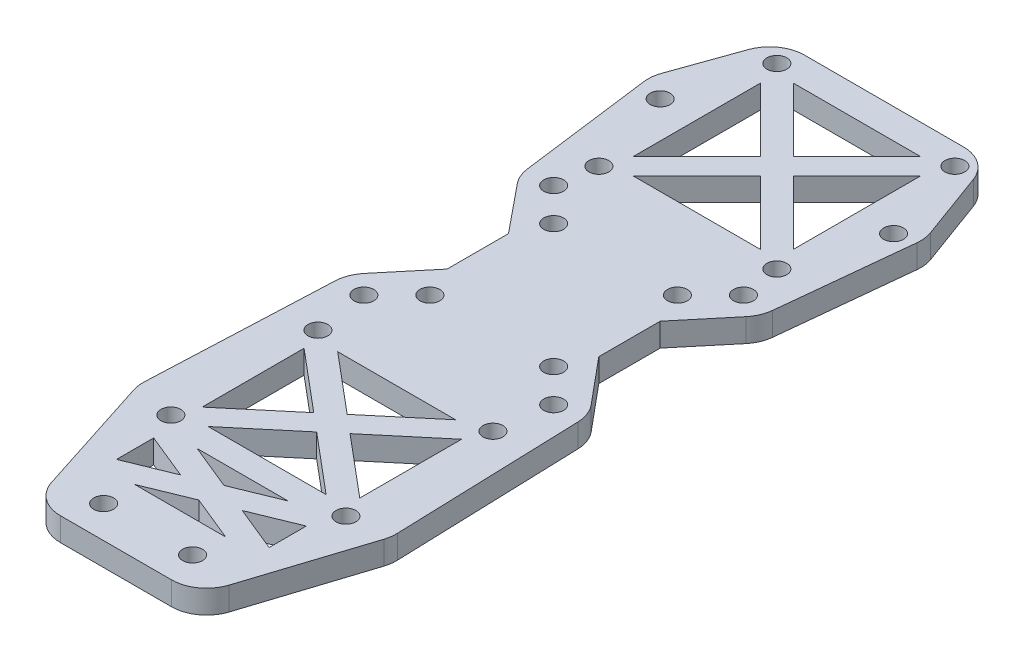
SolidWorks part; units mm, degrees
ref_plane "Front Plane" through (0, 0, 0) normal (0, 0, 1) x (1, 0, 0)
ref_plane "Top Plane" through (0, 0, 0) normal (0, 1, 0) x (1, 0, 0)
ref_plane "Right Plane" through (0, 0, 0) normal (1, 0, 0) x (0, 0, -1)
sketch "Sketch1" plane through (0, 0, 0) normal (0, 1, 0) x (1, 0, 0)
  line L22 (0, 8) -> (0, 23) construction
  line L23 (-10.5, -8) -> (10.5, -8) construction
  line L24 (-10.5, -8) -> (-10.5, 8) construction
  line L25 (-10.5, 8) -> (10.5, 8) construction
  line L26 (10.5, -8) -> (10.5, 8) construction
  line L27 (-20, 20) -> (-69.4975, 69.4975) construction
  line L28 (-20, -20) -> (-69.4975, -69.4975) construction
  line L29 (0, -8) -> (0, -38) construction
  line L31 (-15.25, 23) -> (15.25, 23) construction
  line L32 (-15.25, 23) -> (-15.25, 53.5) construction
  line L33 (-15.25, 53.5) -> (15.25, 53.5) construction
  line L34 (15.25, 23) -> (15.25, 53.5) construction
  line L35 (-15.25, 23) -> (15.25, 53.5) construction
  line L36 (-15.25, 53.5) -> (15.25, 23) construction
  line L41 (-2.2741, -34.7838) -> (-12.1911, -26.4535)
  line L42 (-1.5547, -38) -> (-13.4775, -48.0151)
  line L45 (20, -20) -> (69.4975, -69.4975) construction
  line L46 (-9.5155, -74.9948) -> (9.5155, -74.9948)
  line L53 (0, 95) -> (0, -95) construction
  line L59 (-20, -75) -> (20, 75) construction
  line L60 (-20, 75) -> (20, -75) construction
  line L61 (20, 20) -> (-20, -20) construction
  line L62 (-1.5547, -38) -> (1.5547, -38)
  line L63 (0, -35.152) -> (0, -40.848)
  line L64 (20, -20) -> (-20, 20) construction
  line L66 (0, -35.152) -> (-5.3238, -20.9553)
  line L69 (20, 20) -> (69.4975, 69.4975) construction
  line L70 (-14.1084, 57.113) -> (13.1312, 57.113)
  line L71 (2.2741, -34.7838) -> (7.1964, -21.6575)
  line L72 (0, -35.152) -> (5.3238, -20.9553)
  line L73 (1.5547, -38) -> (13.4775, -48.0151)
  line L74 (1.5547, -38) -> (13.4775, -27.9849)
  line L75 (-2.2741, -34.7838) -> (-7.1964, -21.6575)
  line L76 (2.2741, -34.7838) -> (12.1911, -26.4535)
  line L77 (2.2741, -41.2162) -> (7.1964, -54.3425)
  line L78 (-1.5547, -38) -> (-13.4775, -27.9849)
  line L79 (-2.2741, -41.2162) -> (-7.1964, -54.3425)
  line L80 (-2.2741, -41.2162) -> (-12.1911, -49.5465)
  line L81 (0, -40.848) -> (5.3238, -55.0447)
  line L82 (0, -40.848) -> (-5.3238, -55.0447)
  line L83 (2.2741, -41.2162) -> (12.1911, -49.5465)
  line L84 (20, 0) -> (-20, 0) construction
  line L86 (-13, -5.2632) -> (-13, 5.2632)
  line L87 (13, -5.2632) -> (13, 5.2632)
  line L92 (-13, -8) -> (-13, 8) construction
  line L93 (13, -8) -> (13, 8) construction
  line L95 (-26.1774, -26.1774) -> (26.1774, -26.1774) construction
  line L96 (-26.1774, -26.1774) -> (-26.1774, 26.1774) construction
  line L97 (-26.1774, 26.1774) -> (26.1774, 26.1774) construction
  line L98 (26.1774, -26.1774) -> (26.1774, 26.1774) construction
  line L99 (-26.1774, -26.1774) -> (26.1774, 26.1774) construction
  line L100 (-26.1774, 26.1774) -> (26.1774, -26.1774) construction
  line L101 (-19.7604, 53.1268) -> (-23.659, 42.1845)
  line L102 (-13, 5.2632) -> (-19.6727, 13.4492)
  line L103 (-15.2273, -70.8321) -> (-21.92, -50.0261)
  line L104 (-13, -5.2632) -> (-19.4568, -13.0215)
  line L105 (15.2273, -70.8321) -> (21.6746, -50.7889)
  line L106 (13, -5.2632) -> (19.5205, -13.0981)
  line L107 (13, 5.2632) -> (19.6704, 13.2781)
  line L108 (18.7641, 53.1794) -> (23.0196, 41.5787)
  line L109 (-23.9568, 39.3962) -> (-20.9718, 16.4656)
  line L110 (21.0264, 16.4959) -> (23.3545, 38.892)
  line L111 (21.9596, -48.7542) -> (20.9055, -16.7388)
  line L112 (-22.2025, -47.928) -> (-20.8394, -16.5988)
  circle A4 centre (15.25, 53.5) radius 1.4712 construction
  circle A5 centre (15.25, 23) radius 1.6691 construction
  circle A6 centre (-15.25, 23) radius 1.8297 construction
  circle A7 centre (-15.25, 53.5) radius 1.9203 construction
  arc A12 (-12.1911, -26.4535) -> (-13.4775, -27.9849) centre (-15, -25.4) ccw
  arc A13 (12.1911, -26.4535) -> (13.4775, -27.9849) centre (15, -25.4) cw
  arc A14 (12.1911, -49.5465) -> (13.4775, -48.0151) centre (15, -50.6) ccw
  arc A15 (-12.1911, -49.5465) -> (-13.4775, -48.0151) centre (-15, -50.6) cw
  arc A16 (7.1964, -21.6575) -> (5.3238, -20.9553) centre (7.62, -17.68) ccw
  arc A17 (-5.3238, -20.9553) -> (-7.1964, -21.6575) centre (-7.62, -17.68) ccw
  arc A18 (-7.1964, -54.3425) -> (-5.3238, -55.0447) centre (-7.62, -58.32) ccw
  arc A19 (5.3238, -55.0447) -> (7.1964, -54.3425) centre (7.62, -58.32) ccw
  arc A30 (-14.1084, 57.113) -> (-19.7604, 53.1268) centre (-14.1084, 51.113) ccw
  arc A31 (13.1312, 57.113) -> (18.7641, 53.1794) centre (13.1312, 51.113) cw
  circle A32 centre (-7.62, -69.4975) radius 1.7273
  circle A33 centre (7.62, -69.4975) radius 1.8852
  arc A34 (15.2273, -70.8321) -> (9.5155, -74.9948) centre (9.5155, -68.9948) cw
  arc A35 (-15.2273, -70.8321) -> (-9.5155, -74.9948) centre (-9.5155, -68.9948) ccw
  circle A38 centre (-20, 38.25) radius 1.5
  circle A39 centre (20, 38.25) radius 1.5
  arc A40 (21.9596, -48.7542) -> (21.6746, -50.7889) centre (15.9628, -48.9516) cw
  arc A41 (-22.2025, -47.928) -> (-21.92, -50.0261) centre (-16.2082, -48.1888) ccw
  arc A42 (-20.8394, -16.5988) -> (-19.4568, -13.0215) centre (-14.845, -16.8597) cw
  arc A43 (20.9055, -16.7388) -> (19.5205, -13.0981) centre (14.9087, -16.9362) ccw
  arc A44 (23.3545, 38.892) -> (23.0196, 41.5787) centre (17.3867, 39.5123) ccw
  arc A45 (21.0264, 16.4959) -> (19.6704, 13.2781) centre (15.0586, 17.1163) cw
  arc A46 (-20.9718, 16.4656) -> (-19.6727, 13.4492) centre (-15.022, 17.2401) ccw
  arc A47 (-23.9568, 39.3962) -> (-23.659, 42.1845) centre (-18.007, 40.1708) cw
  point P0 (0, 0)
  point P1 (0, 0)
  point P2 (0, 0)
  point P6 (0, -38)
  point P9 (0, 0)
  point P17 (0, 38.25)
  point P83 (0, 0)
  dimension "D42" = 3
  dimension "D43" = 3
  dimension "D44" = 4
  dimension "D45" = 4
  dimension "D46" = 3
  dimension "D47" = 3
  dimension "D48" = 4
  dimension "D49" = 4
  dimension "D51" = 6
  dimension "D52" = 6
  dimension "D55" = 6
  dimension "D59" = 6
  dimension "D60" = 3
  dimension "D1" = 21
  dimension "D3" = 40
  dimension "D4" = 16
  dimension "D5" = 15
  dimension "D6" = 30
  dimension "D7" = 30.5
  dimension "D8" = 30.5
  dimension "D9" = 0
  dimension "D10" = 70
  dimension "D11" = 70
  dimension "D12" = 45
  dimension "D13" = 45
  dimension "D14" = 70
  dimension "D15" = 70
  dimension "D16" = 19.5898
  dimension "D17" = 21.7018
  dimension "D18" = 20.32
  dimension "D19" = 12.6
  dimension "D20" = 19.5898
  dimension "D21" = 0
  dimension "D22" = 150
  dimension "D23" = 21.7018
  dimension "D24" = 21.7018
  dimension "D25" = 19.5898
  dimension "D26" = 15.5709
  dimension "D27" = 12.9514
  dimension "D28" = 13.1263
  dimension "D29" = 15.1621
  dimension "D30" = 15.1621
  dimension "D31" = 14.0189
  dimension "D32" = 12.9514
  dimension "D33" = 15.5709
  dimension "D34" = 15.5709
  dimension "D35" = 12.9514
  dimension "D36" = 14.0189
  dimension "D37" = 15.1621
  dimension "D38" = 15.1621
  dimension "D39" = 14.0189
  dimension "D40" = 12.9514
  dimension "D41" = 15.5709
  dimension "D50" = 0
  dimension "D61" = 20
  dimension "D62" = 18.25
  dimension "D63" = 18.25
  dimension "D64" = 20
  dimension "D53" = 2.5
  dimension "D54" = 2.5
extrude "Boss-Extrude1" add sketch "Sketch1" along normal blind 4 contours L70 A31 L108 A44 L110 A45 L107 L87 L106 A43 L111 A40 L105 A34 L46 A35 L103 A41 L112 A42 L104 L86 L102 A46 L109 A47 L101 A30
sketch "Sketch7" plane through (0, 4, 0) normal (0, 1, 0) x (1, 0, 0)
  point P0 (7.62, -69.4975)
  point P2 (-7.62, -69.4975)
  point P4 (-26.1774, -26.1774)
  point P6 (26.1774, -26.1774)
  point P8 (26.1774, 26.1774)
  point P10 (-26.1774, 26.1774)
  point P13 (-15, -25.4)
  point P15 (-15.25, 23)
  point P17 (-15.25, 53.5)
  point P19 (15.25, 53.5)
  point P21 (15.25, 23)
  point P23 (-15, -50.6)
  point P25 (15, -50.6)
  point P27 (15, -25.4)
  point P30 (20, 38.25)
  point P32 (-20, 38.25)
sketch "Sketch6" plane through (0, 4, 0) normal (0, 1, 0) x (1, 0, 0)
  line L0 (-9.5155, -74.9948) -> (9.5155, -74.9948) construction
  line L1 (-15.25, 23) -> (15.25, 23) construction
  line L2 (-15.25, 23) -> (-15.25, 53.5) construction
  line L3 (-15.25, 53.5) -> (15.25, 53.5) construction
  line L4 (15.25, 23) -> (15.25, 53.5) construction
  line L5 (-15, -50.6) -> (15, -50.6) construction
  line L6 (-15, -50.6) -> (-15, -25.4) construction
  line L7 (-15, -25.4) -> (15, -25.4) construction
  line L8 (15, -50.6) -> (15, -25.4) construction
  line L9 (-9.5155, -74.9948) -> (9.5155, -74.9948)
  line L12 (-15, -50.6) -> (15, -25.4) construction
  line L13 (-15, -25.4) -> (15, -50.6) construction
  line L14 (-13.75, 24.5) -> (13.75, 52) construction
  line L15 (-10.9216, 24.5) -> (10.9216, 24.5)
  line L16 (0, 200095) -> (0, -200095) construction
  line L17 (-7.7916, -53.3037) -> (7.7916, -53.3037)
  line L18 (-13.0763, -55.4644) -> (-13.0763, -61.8357)
  line L19 (13.75, 27.3284) -> (2.8284, 38.25)
  line L20 (-10.9216, 24.5) -> (0, 35.4216)
  line L21 (-13.5, -29.272) -> (-3.1095, -38)
  line L22 (-10.1048, -49.1) -> (0, -40.612)
  line L24 (-7.7916, -63.9964) -> (7.7916, -63.9964)
  line L26 (10.9216, 24.5) -> (0, 35.4216)
  line L27 (-13.75, 27.3284) -> (-2.8284, 38.25)
  line L28 (-13.5, -46.728) -> (-13.5, -29.272)
  line L29 (-13.5, -46.728) -> (-3.1095, -38)
  line L32 (13.0763, -55.4644) -> (13.0763, -61.8357)
  line L33 (-13.75, 27.3284) -> (-13.75, 49.1716)
  line L34 (0, 41.0784) -> (10.9216, 52)
  line L35 (-2.8284, 38.25) -> (-13.75, 49.1716)
  line L36 (2.8284, 38.25) -> (13.75, 49.1716)
  line L37 (0, 41.0784) -> (-10.9216, 52)
  line L38 (-10.1048, -26.9) -> (10.1048, -26.9)
  line L39 (-13.75, 23) -> (-13.75, 53.5) construction
  line L40 (-10.9216, 52) -> (10.9216, 52)
  line L41 (-15.25, 23) -> (15.25, 53.5) construction
  line L42 (0, -35.388) -> (10.1048, -26.9)
  line L43 (-16.6642, 24.4142) -> (13.8358, 54.9142) construction
  line L44 (-10.1048, -49.1) -> (10.1048, -49.1)
  line L45 (-13.8358, 21.5858) -> (16.6642, 52.0858) construction
  line L46 (13.75, 24.5) -> (-13.75, 52) construction
  line L47 (13.75, 27.3284) -> (13.75, 49.1716)
  line L48 (0, -40.612) -> (10.1048, -49.1)
  line L49 (-16.2864, -26.9314) -> (13.7136, -52.1314) construction
  line L50 (-15, -26.9) -> (15, -26.9) construction
  line L51 (3.1095, -38) -> (13.5, -29.272)
  line L52 (-10.1048, -26.9) -> (0, -35.388)
  line L53 (-16.2864, -49.0686) -> (13.7136, -23.8686) construction
  line L54 (-13.7136, -52.1314) -> (16.2864, -26.9314) construction
  line L55 (-15, -49.1) -> (15, -49.1) construction
  line L56 (13.5, -46.728) -> (13.5, -29.272)
  line L57 (3.1095, -38) -> (13.5, -46.728)
  line L58 (-13.0763, -53.3037) -> (13.0763, -63.9964) construction
  line L59 (-13.0763, -63.9964) -> (13.0763, -53.3037) construction
  line L60 (-7.7916, -63.9964) -> (0, -60.8108)
  line L61 (-13.0763, -55.4644) -> (-5.2847, -58.6501)
  line L62 (-13.0763, -61.8357) -> (-5.2847, -58.6501)
  line L63 (-7.7916, -53.3037) -> (0, -56.4893)
  line L64 (-12.3194, -51.4524) -> (13.8332, -62.1452) construction
  line L65 (-13.8332, -55.1549) -> (12.3194, -65.8477) construction
  line L66 (-13.8332, -62.1452) -> (12.3194, -51.4524) construction
  line L67 (-12.3194, -65.8477) -> (13.8332, -55.1549) construction
  line L68 (0, -60.8108) -> (7.7916, -63.9964)
  line L69 (0, -56.4893) -> (7.7916, -53.3037)
  line L70 (5.2847, -58.6501) -> (13.0763, -61.8357)
  line L71 (5.2847, -58.6501) -> (13.0763, -55.4644)
  point P24 (0, -58.6501)
  dimension "D1" = 2
  dimension "D2" = 2
  dimension "D3" = 2
  dimension "D4" = 1.5
  dimension "D5" = 1.5
  dimension "D6" = 1.5
  dimension "D7" = 2
extrude "Cut-Extrude1" cut sketch "Sketch6" against normal blind 10 contours L40 L37 L34 | L19 L47 L36 | L27 L35 L33 | L15 L26 L20 | L51 L57 L56 | L38 L52 L42 | L28 L29 L21 | L48 L22 L44 | L18 L62 L61 | L63 L69 L17 | L71 L70 L32 | L68 L60 L24 region at (0, 4, -28.1405) region at (0, 4, 54.3656) region at (-10.4791, 4, 58.6501) region at (10.1095, 4, -38.25) region at (-10.0365, 4, 38) region at (0, 4, 46.2707) region at (0, 4, 62.9345) region at (-10.1095, 4, -38.25) region at (10.4791, 4, 58.6501) region at (0, 4, -48.3595) region at (0, 4, 29.7293) region at (10.0365, 4, 38)
hole_wizard "M3 Clearance Hole3" positions "Sketch7" profile "Sketch9" hole size "M3" standard "ISO" end condition through all
sketch "Sketch9" plane through (7.62, 4, 69.4975) normal (1, 0, 0) x (0, 0, 1)
  line L0 (0, 0) -> (0, 4)
  line L1 (0, 4) -> (1.7, 4)
  line L2 (1.7, 4) -> (1.7, 0)
  line L5 (1.7, 0) -> (0, 0)
  line L11 (0, -6.35) -> (0, 107.95) construction
  dimension "Thru Hole Dia." = 3.4
  dimension "Thru Hole Depth" = 4
sketch "Sketch13" plane through (0, 4, 0) normal (0, 1, 0) x (1, 0, 0)
  line L0 (-13, 0) -> (13, 0) construction
  line L1 (-13, -5.2632) -> (-13, 5.2632) construction
  line L2 (13, -5.2632) -> (13, 5.2632) construction
  line L3 (0, 24.5) -> (0, -26.9) construction
  line L4 (-10.9216, 24.5) -> (10.9216, 24.5) construction
  line L5 (-10.1048, -26.9) -> (10.1048, -26.9) construction
  line L6 (0, 0) -> (-10.6066, 10.6066) construction
  line L7 (-10.6066, 10.6066) -> (-16.2635, 16.2635) construction
  circle A0 centre (-10.6066, 10.6066) radius 1.7
  circle A1 centre (-16.2635, 16.2635) radius 1.7
  circle A2 centre (10.6066, 10.6066) radius 1.7
  circle A3 centre (16.2635, 16.2635) radius 1.7
  circle A4 centre (16.2635, -16.2635) radius 1.7
  circle A5 centre (10.6066, -10.6066) radius 1.7
  circle A6 centre (-10.6066, -10.6066) radius 1.7
  circle A7 centre (-16.2635, -16.2635) radius 1.7
  point P13 (-10.6066, 10.6066)
  point P15 (-16.2635, 16.2635)
  point P19 (10.6066, 10.6066)
  point P21 (16.2635, 16.2635)
  point P23 (16.2635, -16.2635)
  point P25 (10.6066, -10.6066)
  point P27 (-10.6066, -10.6066)
  point P29 (-16.2635, -16.2635)
  point P39 (-10.6066, 10.6066)
  dimension "D2" = 3.4
  dimension "D3" = 3.4
  dimension "D1" = 15
  dimension "D5" = 8
hole_wizard "M3 Clearance Hole4" positions "Sketch13" profile "Sketch15" hole size "M3" standard "ISO" end condition through all
sketch "Sketch15" plane through (-10.6066, 4, -10.6066) normal (1, 0, 0) x (0, 0, 1)
  line L0 (0, 0) -> (0, 4)
  line L1 (0, 4) -> (1.7, 4)
  line L2 (1.7, 4) -> (1.7, 0)
  line L5 (1.7, 0) -> (0, 0)
  line L11 (0, -6.35) -> (0, 107.95) construction
  dimension "Thru Hole Dia." = 3.4
  dimension "Thru Hole Depth" = 4
